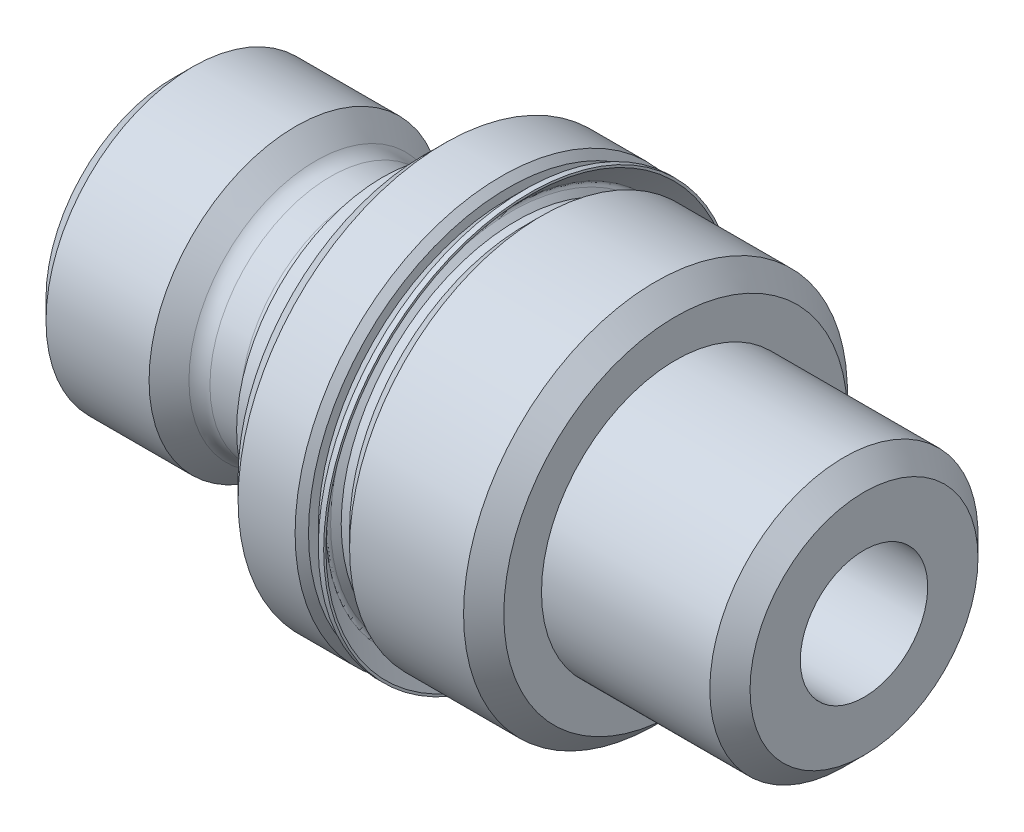
SolidWorks part; units mm, degrees
material "Cast Alloy Steel"
ref_plane "Front Plane" through (0, 0, 0) normal (0, 0, 1) x (1, 0, 0)
ref_plane "Top Plane" through (0, 0, 0) normal (0, 1, 0) x (1, 0, 0)
ref_plane "Right Plane" through (0, 0, 0) normal (1, 0, 0) x (0, 0, -1)
sketch "Sketch1" plane through (0, 0, 0) normal (0, 0, 1) x (1, 0, 0)
  line L0 (0, 0) -> (0, 4.8006)
  line L1 (0, 4.8006) -> (0.7557, 5.5563)
  line L2 (0.7557, 5.5563) -> (4.6603, 5.5563)
  line L3 (4.6603, 5.5563) -> (5.4181, 4.8042)
  line L4 (5.9817, 4.572) -> (7.1501, 4.572)
  line L5 (7.9502, 5.3721) -> (7.9502, 5.5309)
  line L6 (7.9502, 5.5309) -> (9.525, 5.5309)
  line L7 (9.525, 5.5309) -> (9.525, 0)
  line L8 (9.525, 0) -> (0, 0)
  line L9 (9.525, 0) -> (0, 0) construction
  arc A0 (5.4181, 4.8042) -> (5.9817, 4.572) centre (5.9817, 5.3721) ccw
  arc A1 (7.1501, 4.572) -> (7.9502, 5.3721) centre (7.1501, 5.3721) ccw
revolve "Revolve1" add sketch "Sketch1" angle 360 about L9 reverse direction yes
cosmetic thread "Cosmetic Thread1" parameters "D1"=5.4159, "D2"=9.6012
sketch "Sketch2" plane through (0, 0, 0) normal (0, 0, 1) x (1, 0, 0)
  line L0 (9.525, 0) -> (9.525, 7.0485)
  line L1 (9.525, 7.0485) -> (10.287, 7.8105)
  line L2 (10.287, 7.8105) -> (12.446, 7.8105)
  line L3 (12.446, 7.8105) -> (12.7, 7.5565)
  line L4 (12.7, 7.5565) -> (12.7, 6.6357)
  line L5 (12.7, 6.6357) -> (13.335, 6.6357)
  line L6 (13.335, 6.6357) -> (13.97, 7.2707)
  line L7 (13.97, 7.2707) -> (18.288, 7.2707)
  line L8 (18.288, 7.2707) -> (19.05, 6.5088)
  line L9 (19.05, 6.5088) -> (19.05, 0)
  line L10 (19.05, 0) -> (9.525, 0)
  line L11 (19.05, 0) -> (9.525, 0) construction
revolve "Revolve2" add sketch "Sketch2" angle 360 about L11 reverse direction yes
sketch "Sketch3" plane through (0, 0, 0) normal (0, 0, 1) x (1, 0, 0)
  line L0 (19.05, 0) -> (19.05, 5.08)
  line L1 (19.05, 5.08) -> (25.4254, 5.08)
  line L2 (25.4254, 5.08) -> (26.1874, 4.318)
  line L3 (26.1874, 4.318) -> (26.1874, 0)
  line L4 (26.1874, 0) -> (19.05, 0)
  line L5 (26.1874, 0) -> (19.05, 0) construction
revolve "Revolve3" add sketch "Sketch3" angle 360 about L5 reverse direction yes
hole_wizard "Hole1" positions "Sketch5" profile "Sketch4" legacy
sketch "Sketch5" plane through (0, 0, 0) normal (-1, 0, 0) x (0, 0, 1)
  point P0 (0, 0)
sketch "Sketch4" plane through (0, 0, 0) normal (0, 1, 0) x (0, 0, 1)
  line L0 (0, 0) -> (0, 26.1874)
  line L1 (0, 26.1874) -> (2.413, 26.1874)
  line L2 (2.413, 26.1874) -> (2.413, 0.508)
  line L3 (2.413, 0.508) -> (2.921, 0)
  line L4 (2.921, 0) -> (0, 0)
  line L5 (0, -6.4453) -> (0, 115.525) construction
  line L6 (-2.413, 0.508) -> (-2.921, 0) construction
  dimension "Diameter" = 4.826
  dimension "Depth" = 26.1874
  dimension "C-Sink Angle" = 90
  dimension "C-Sink Diameter" = 5.842
ref_plane "Plane1" through (0, 0, 0) normal (1, 0, 0) x (0, 0, -1)
ref_plane "Plane2" through (0, 0, 0) normal (1, 0, 0) x (0, 0, -1)
ref_plane "Plane3" through (0, 0, 0) normal (0, -0.7071, 0.7071) x (1, 0, 0)
ref_plane "Plane4" through (0, 0, 0) normal (1, 0, 0) x (0, 0, -1)
ref_plane "Plane5" through (12.7, 0, 0) normal (1, 0, 0) x (0, 0, -1)
ref_plane "Plane6" through (9.525, 0, 0) normal (1, 0, 0) x (0, 0, -1)
ref_plane "Plane7" through (12.7, 0, 0) normal (1, 0, 0) x (0, 0, -1)
sketch "Sketch6" plane through (0, 0, 0) normal (0, 0, 1) x (1, 0, 0)
  line L0 (12.7, 6.3818) -> (13.335, 6.3818)
  line L1 (13.335, 6.3818) -> (13.335, 6.6357)
  line L2 (13.335, 6.6357) -> (13.0175, 6.6357)
  line L3 (13.0175, 6.6357) -> (12.817, 6.8362)
  line L4 (12.817, 7.0158) -> (13.5276, 7.7263)
  line L5 (13.5276, 7.7263) -> (13.5276, 7.8105)
  line L6 (13.5276, 7.8105) -> (13.3244, 7.8105)
  line L7 (13.3244, 7.8105) -> (12.7, 7.1861)
  line L8 (12.7, 7.1861) -> (12.7, 6.3818)
  line L9 (13.335, 0) -> (12.7, 0) construction
  arc A0 (12.817, 6.8362) -> (12.817, 7.0158) centre (12.9068, 6.926) cw
revolve "Revolve4" add sketch "Sketch6" angle 360 about L9 reverse direction yes
ref_plane "Plane8" through (13.335, 0, 0) normal (1, 0, 0) x (0, 0, -1)
ref_plane "Plane9" through (9.525, 0, 0) normal (1, 0, 0) x (0, 0, -1)
ref_plane "Plane10" through (7.9502, 0, 0) normal (1, 0, 0) x (0, 0, -1)
ref_plane "Plane11" through (0, 0, 0) normal (0, 1, 0) x (1, 0, 0)
ref_plane "Plane12" through (0, 0, 0) normal (0, 1, 0) x (1, 0, 0)
ref_plane "Plane13" through (9.525, 0, 0) normal (1, 0, 0) x (0, 0, -1)
ref_plane "Plane14" through (0, 0, 0) normal (0, 1, 0) x (1, 0, 0)
ref_plane "Plane15" through (0, 0, 0) normal (0, 1, 0) x (1, 0, 0)
ref_plane "Plane16" through (0, 0, 0) normal (0, 1, 0) x (1, 0, 0)
ref_plane "Plane17" through (0, 0, 0) normal (1, 0, 0) x (0, 0, -1)
ref_plane "dp1 XY" through (0, 0, 0) normal (0, 0, 1) x (1, 0, 0)
ref_plane "dp1 XZ" through (0, 5.5309, 0) normal (0, -1, 0) x (-1, 0, 0)
ref_plane "dp1 YZ" through (9.525, 0, 0) normal (1, 0, 0) x (0, 0, -1)
ref_axis "dp1 X" through (-80.9, 5.5309, 0) along (1, 0, 0)
ref_axis "dp1 Y" through (9.525, -50, 0) along (0, 1, 0)
ref_axis "dp1 Z" through (9.525, 5.5309, 80.9) along (0, 0, -1)
sketch3d "dp1"
  point P0 (9.525, 5.5309, 0)
ref_plane "dp2 XY" through (0, 0, 0) normal (0, 0, 1) x (1, 0, 0)
ref_plane "dp2 XZ" through (0, -5.5309, 0) normal (0, -1, 0) x (-1, 0, 0)
ref_plane "dp2 YZ" through (9.525, 0, 0) normal (1, 0, 0) x (0, 0, -1)
ref_axis "dp2 X" through (-80.9, -5.5309, 0) along (1, 0, 0)
ref_axis "dp2 Y" through (9.525, -50, 0) along (0, 1, 0)
ref_axis "dp2 Z" through (9.525, -5.5309, 80.9) along (0, 0, -1)
sketch3d "dp2"
  point P0 (9.525, -5.5309, 0)
ref_plane "rod_guide XY" through (0, 0, 0) normal (1, 0, 0) x (0, 0, -1)
ref_plane "rod_guide XZ" through (0, 0, 0) normal (0, -1, 0) x (-1, 0, 0)
ref_plane "rod_guide YZ" through (0, 0, 0) normal (0, 0, -1) x (-1, 0, 0)
ref_axis "rod_guide X" through (0, 0, 80.9) along (0, 0, -1)
ref_axis "rod_guide Y" through (0, -50, 0) along (0, 1, 0)
ref_axis "rod_guide Z" through (80.9, 0, 0) along (-1, 0, 0)
sketch3d "rod_guide"
  point P0 (0, 0, 0)
ref_plane "s1 XY" through (0, 0, 0) normal (0, 0, 1) x (1, 0, 0)
ref_plane "s1 XZ" through (0, 0, 0) normal (0, -1, 0) x (-1, 0, 0)
ref_plane "s1 YZ" through (7.9502, 0, 0) normal (1, 0, 0) x (0, 0, -1)
ref_axis "s1 X" through (-80.9, 0, 0) along (1, 0, 0)
ref_axis "s1 Y" through (7.9502, -50, 0) along (0, 1, 0)
ref_axis "s1 Z" through (7.9502, 0, 80.9) along (0, 0, -1)
sketch3d "s1"
  point P0 (7.9502, 0, 0)
ref_plane "s2 XY" through (0, 0, 0) normal (0, 0, 1) x (1, 0, 0)
ref_plane "s2 XZ" through (0, 0, 0) normal (0, -1, 0) x (-1, 0, 0)
ref_plane "s2 YZ" through (9.525, 0, 0) normal (1, 0, 0) x (0, 0, -1)
ref_axis "s2 X" through (-80.9, 0, 0) along (1, 0, 0)
ref_axis "s2 Y" through (9.525, -50, 0) along (0, 1, 0)
ref_axis "s2 Z" through (9.525, 0, 80.9) along (0, 0, -1)
sketch3d "s2"
  point P0 (9.525, 0, 0)
ref_plane "t1 XY" through (9.525, 0, 0) normal (1, 0, 0) x (0, 0, -1)
ref_plane "t1 XZ" through (0, 0, 0) normal (0, -1, 0) x (-1, 0, 0)
ref_plane "t1 YZ" through (0, 0, 0) normal (0, 0, -1) x (-1, 0, 0)
ref_axis "t1 X" through (9.525, 0, 80.9) along (0, 0, -1)
ref_axis "t1 Y" through (9.525, -50, 0) along (0, 1, 0)
ref_axis "t1 Z" through (80.9, 0, 0) along (-1, 0, 0)
sketch3d "t1"
  point P0 (9.525, 0, 0)
ref_plane "t111 XY" through (9.525, 0, 0) normal (1, 0, 0) x (0, 0, -1)
ref_plane "t111 XZ" through (0, 0, 0) normal (0, -1, 0) x (-1, 0, 0)
ref_plane "t111 YZ" through (0, 0, 0) normal (0, 0, -1) x (-1, 0, 0)
ref_axis "t111 X" through (9.525, 0, 80.9) along (0, 0, -1)
ref_axis "t111 Y" through (9.525, -50, 0) along (0, 1, 0)
ref_axis "t111 Z" through (80.9, 0, 0) along (-1, 0, 0)
sketch3d "t111"
  point P0 (9.525, 0, 0)
ref_plane "to_foot_bracket XY" through (9.525, 0, 0) normal (1, 0, 0) x (0, 0, -1)
ref_plane "to_foot_bracket XZ" through (0, 0, 0) normal (0, -1, 0) x (-1, 0, 0)
ref_plane "to_foot_bracket YZ" through (0, 0, 0) normal (0, 0, -1) x (-1, 0, 0)
ref_axis "to_foot_bracket X" through (9.525, 0, 80.9) along (0, 0, -1)
ref_axis "to_foot_bracket Y" through (9.525, -50, 0) along (0, 1, 0)
ref_axis "to_foot_bracket Z" through (80.9, 0, 0) along (-1, 0, 0)
sketch3d "to_foot_bracket"
  point P0 (9.525, 0, 0)
ref_plane "to_nut XY" through (7.9502, 0, 0) normal (1, 0, 0) x (0, 0, -1)
ref_plane "to_nut XZ" through (0, 0, 0) normal (0, -1, 0) x (-1, 0, 0)
ref_plane "to_nut YZ" through (0, 0, 0) normal (0, 0, -1) x (-1, 0, 0)
ref_axis "to_nut X" through (7.9502, 0, 80.9) along (0, 0, -1)
ref_axis "to_nut Y" through (7.9502, -50, 0) along (0, 1, 0)
ref_axis "to_nut Z" through (80.9, 0, 0) along (-1, 0, 0)
sketch3d "to_nut"
  point P0 (7.9502, 0, 0)
ref_plane "to_rod XY" through (0, 0, 0) normal (1, 0, 0) x (0, 0, -1)
ref_plane "to_rod XZ" through (0, 0, 0) normal (0, -1, 0) x (-1, 0, 0)
ref_plane "to_rod YZ" through (0, 0, 0) normal (0, 0, -1) x (-1, 0, 0)
ref_axis "to_rod X" through (0, 0, 80.9) along (0, 0, -1)
ref_axis "to_rod Y" through (0, -50, 0) along (0, 1, 0)
ref_axis "to_rod Z" through (80.9, 0, 0) along (-1, 0, 0)
sketch3d "to_rod"
  point P0 (0, 0, 0)
ref_plane "to_screw XY" through (0, 0, 0) normal (0, 1, 0) x (1, 0, 0)
ref_plane "to_screw XZ" through (0, 0, 0) normal (0, 0, 1) x (1, 0, 0)
ref_plane "to_screw YZ" through (15.875, 0, 0) normal (1, 0, 0) x (0, 0, -1)
ref_axis "to_screw X" through (-80.9, 0, 0) along (1, 0, 0)
ref_axis "to_screw Y" through (15.875, 0, 50) along (0, 0, -1)
ref_axis "to_screw Z" through (15.875, 50, 0) along (0, -1, 0)
sketch3d "to_screw"
  point P0 (15.875, 0, 0)
ref_plane "to_trunnion_brackets XY" through (0, 0, 0) normal (0, 1, 0) x (1, 0, 0)
ref_plane "to_trunnion_brackets XZ" through (0, 0, 0) normal (0, 0, 1) x (1, 0, 0)
ref_plane "to_trunnion_brackets YZ" through (0, 0, 0) normal (1, 0, 0) x (0, 0, -1)
ref_axis "to_trunnion_brackets X" through (-80.9, 0, 0) along (1, 0, 0)
ref_axis "to_trunnion_brackets Y" through (0, 0, 50) along (0, 0, -1)
ref_axis "to_trunnion_brackets Z" through (0, 50, 0) along (0, -1, 0)
sketch3d "to_trunnion_brackets"
  point P0 (0, 0, 0)
ref_plane "to_trunnion_brackets1 XY" through (0, 0, 0) normal (0, 1, 0) x (1, 0, 0)
ref_plane "to_trunnion_brackets1 XZ" through (0, 0, 0) normal (0, 0, 1) x (1, 0, 0)
ref_plane "to_trunnion_brackets1 YZ" through (0, 0, 0) normal (1, 0, 0) x (0, 0, -1)
ref_axis "to_trunnion_brackets1 X" through (-80.9, 0, 0) along (1, 0, 0)
ref_axis "to_trunnion_brackets1 Y" through (0, 0, 50) along (0, 0, -1)
ref_axis "to_trunnion_brackets1 Z" through (0, 50, 0) along (0, -1, 0)
sketch3d "to_trunnion_brackets1"
  point P0 (0, 0, 0)
ref_plane "to_trunnion_brackets2 XY" through (0, 0, 0) normal (0, 1, 0) x (1, 0, 0)
ref_plane "to_trunnion_brackets2 XZ" through (0, 0, 0) normal (0, 0, 1) x (1, 0, 0)
ref_plane "to_trunnion_brackets2 YZ" through (0, 0, 0) normal (1, 0, 0) x (0, 0, -1)
ref_axis "to_trunnion_brackets2 X" through (-80.9, 0, 0) along (1, 0, 0)
ref_axis "to_trunnion_brackets2 Y" through (0, 0, 50) along (0, 0, -1)
ref_axis "to_trunnion_brackets2 Z" through (0, 50, 0) along (0, -1, 0)
sketch3d "to_trunnion_brackets2"
  point P0 (0, 0, 0)
ref_plane "to_tube XY" through (13.335, 0, 0) normal (1, 0, 0) x (0, 0, -1)
ref_plane "to_tube XZ" through (0, 0, 0) normal (0, -1, 0) x (-1, 0, 0)
ref_plane "to_tube YZ" through (0, 0, 0) normal (0, 0, -1) x (-1, 0, 0)
ref_axis "to_tube X" through (13.335, 0, 80.9) along (0, 0, -1)
ref_axis "to_tube Y" through (13.335, -50, 0) along (0, 1, 0)
ref_axis "to_tube Z" through (80.9, 0, 0) along (-1, 0, 0)
sketch3d "to_tube"
  point P0 (13.335, 0, 0)
